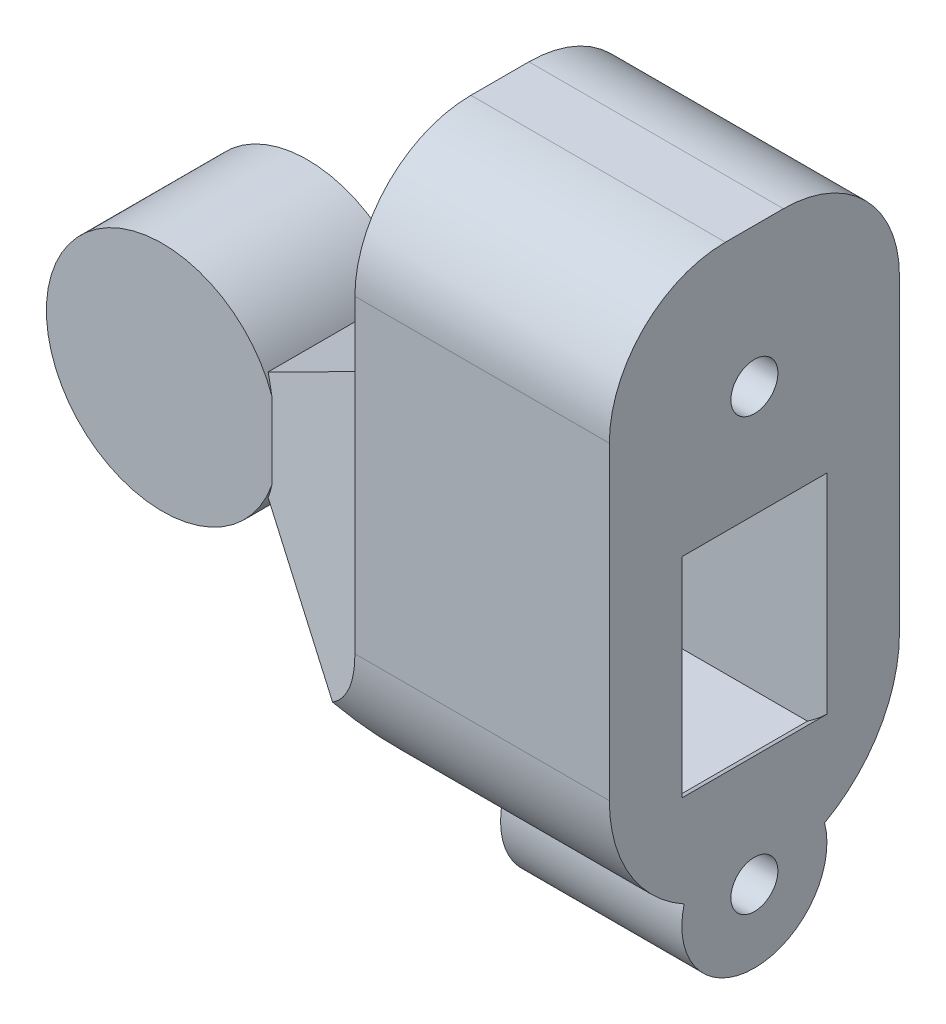
SolidWorks part; units mm, degrees
material "Polycarbonate"
ref_plane "Front Plane" through (0, 0, 0) normal (0, 0, 1) x (1, 0, 0)
ref_plane "Top Plane" through (0, 0, 0) normal (0, 1, 0) x (1, 0, 0)
ref_plane "Right Plane" through (0, 0, 0) normal (1, 0, 0) x (0, 0, -1)
sketch "Sketch1" plane through (0, 0, 0) normal (0, 0, 1) x (1, 0, 0)
  line L3 (4.4873, -2.3813) -> (4.4873, 2.3813)
  arc A0 (4.4873, 2.3813) -> (4.4873, -2.3813) centre (0, 0) ccw
  dimension "D1" = 10.16
  dimension "D2" = 4.7625
extrude "Boss-Extrude1" add sketch "Sketch1" along normal blind 6.35
sketch "Sketch2" plane through (0, 0, 6.35) normal (0, 0, 1) x (1, 0, 0)
  line L1 (21.806, 6.3475) -> (22.74, 7.6311) construction
  line L3 (21.806, -6.3475) -> (22.74, -7.6311) construction
  line L4 (21.806, 6.3475) -> (21.806, -6.3475) construction
  line L5 (4.4873, -2.3813) -> (11.6004, -7.6061)
  line L6 (4.4873, 2.3813) -> (11.6004, 7.6061)
  line L7 (4.4873, 2.3813) -> (4.4873, -2.3813)
  line L9 (22.74, 7.6311) -> (22.74, -7.6311)
  line L10 (14.0937, -9.4375) -> (22.74, -9.4375)
  line L11 (22.74, -9.4375) -> (22.74, -7.6311)
  line L12 (11.6004, -7.6061) -> (14.0937, -9.4375)
  line L13 (11.6004, 7.6061) -> (11.6004, 15.5436)
  line L14 (11.6004, 15.5436) -> (22.74, 15.5436)
  line L16 (4.4873, -2.3813) -> (4.4873, 2.3813) construction
  line L19 (22.74, 7.6311) -> (22.74, 15.5436)
  arc A0 (21.806, 6.3475) -> (21.806, -6.3475) centre (17.1873, 0) ccw construction
  arc A1 (22.74, 7.6311) -> (11.6004, 7.6061) centre (17.1873, 0) ccw construction
  arc A2 (11.6004, -7.6061) -> (22.74, -7.6311) centre (17.1873, 0) ccw construction
  point P9 (21.806, 0)
  point P12 (4.4873, 0)
  line M22 (4.4873, -2.3813) -> (4.4873, 2.3813)
  dimension "D1" = 15.7
  dimension "D2" = 18.875
  dimension "D3" = 12.6949
  dimension "D4" = 12.7
  dimension "D5" = 7.9375
extrude "Boss-Extrude2" add sketch "Sketch2" against normal offset from surface (12.7 mm away) 3.175 from offset 3.175 contours L5 L12 L10 L11 L9 L6 M22 | L10 L11 L9 L19 L14 L13 L6 L7 L5 L12 region at (15.4601, 2.5062, 6.35) up to face at (-0.2963, 0, 0) offset beyond the face yes
sketch "Sketch10" plane through (0, 0, -3.175) normal (0, 0, -1) x (-1, 0, 0)
  line L1 (-22.74, -4.572) -> (-22.74, 4.572)
  line L2 (-22.74, -9.4375) -> (-22.74, 15.5436) construction
  line L3 (-21.8893, -5.2609) -> (-14.7773, -5.2609)
  line L4 (-14.7773, 5.2609) -> (-21.8893, 5.2609)
  line L5 (-12.834, -3.175) -> (-12.834, 3.175)
  arc A0 (-22.74, -4.572) -> (-21.8893, -5.2609) centre (-18.3333, 0) ccw
  arc A1 (-14.7773, -5.2609) -> (-12.834, -3.175) centre (-18.3333, 0) ccw
  arc A2 (-21.8893, 5.2609) -> (-22.74, 4.572) centre (-18.3333, 0) ccw
  arc A3 (-12.834, 3.175) -> (-14.7773, 5.2609) centre (-18.3333, 0) ccw
  circle A4 centre (-18.3333, 0) radius 5.08 construction
  point P3 (-22.74, 0)
  dimension "D1" = 12.7
  dimension "D5" = 10.16
  dimension "D2" = 9.144
  dimension "D3" = 7.112
  dimension "D4" = 6.35
extrude "Cut-Extrude1" cut sketch "Sketch10" against normal blind 6.35 from offset 3.175 offset against normal yes
hole_wizard "#1 Clearance Hole1" positions "Sketch7" profile "Sketch8" hole size "#1" standard "ANSI Inch" end condition through all
sketch "Sketch7" plane through (22.74, 0, 0) normal (1, 0, 0) x (0, 0, -1)
  line L0 (3.175, -9.4375) -> (-9.525, -9.4375) construction
  point P0 (-3.175, 9.4375)
  dimension "D1" = 18.875
sketch "Sketch8" plane through (22.74, 9.4375, 3.175) normal (0, 1, 0) x (0, 0, -1)
  line L0 (0, 0) -> (0, 27.82)
  line L1 (0, 27.82) -> (1.0287, 27.82)
  line L2 (1.0287, 27.82) -> (1.0287, 0)
  line L5 (1.0287, 0) -> (0, 0)
  line L11 (0, -6.35) -> (0, 107.95) construction
  dimension "Thru Hole Dia." = 2.0574
  dimension "Thru Hole Depth" = 27.82
fillet "Fillet4" 2 edges at (18.4169, -9.4375, -3.175) (18.4169, -9.4375, 9.525) type full round first side face at (13.107, 2.8312, -3.175) second side face at (13.107, 2.8312, 9.525) middle face at (18.4169, -9.4375, 3.175)
fillet "Fillet5" radius 5.08 2 edges at (17.1702, 15.5436, 9.525) (17.1702, 15.5436, -3.175)
chamfer "Chamfer3" distance 7.112 angle 25 2 edges at (4.4873, 0, -3.175) (4.4873, 0, 9.525) first distance on face at (11.872, 3.194, -3.175) first distance on face at (11.872, 3.194, 9.525)
sketch "Sketch9" plane through (22.74, 0, 0) normal (1, 0, 0) x (0, 0, -1)
  line L0 (2.414, 13.138) -> (5.4394, 15.2565)
  line L1 (7.2606, 12.6557) -> (3.175, 9.7949)
  line L2 (3.175, -3.0875) -> (3.175, 10.4636) construction
  line L3 (3.175, 9.7949) -> (3.175, 10.4636)
  line L4 (-3.175, 15.5436) -> (9.5717, 15.5436) construction
  line L5 (-1.905, 15.5436) -> (-4.445, 15.5436) construction
  line L6 (-3.175, 15.5436) -> (-3.175, 9.4375) construction
  line L7 (-9.525, 9.7949) -> (-9.525, 10.4636)
  line L8 (-13.6106, 12.6557) -> (-9.525, 9.7949)
  line L9 (-8.764, 13.138) -> (-11.7894, 15.2565)
  arc A0 (3.175, 10.4636) -> (-1.905, 15.5436) centre (-1.905, 10.4636) ccw construction
  arc A1 (5.4394, 15.2565) -> (7.2606, 12.6557) centre (6.35, 13.9561) cw
  arc A2 (3.175, 10.4636) -> (2.414, 13.138) centre (-1.905, 10.4636) ccw
  arc A3 (-9.525, 10.4636) -> (-8.764, 13.138) centre (-4.445, 10.4636) cw
  arc A4 (-11.7894, 15.2565) -> (-13.6106, 12.6557) centre (-12.7, 13.9561) ccw
  dimension "D1" = 1.5875
  dimension "D2" = 125
  dimension "D3" = 9.525
sketch "Sketch11" plane through (22.74, 0, 0) normal (1, 0, 0) x (0, 0, -1)
  arc A0 (-6.2492, -8.6438) -> (-0.1008, -8.6438) centre (-3.175, -9.4375) ccw
  arc A1 (-9.525, -3.0875) -> (3.175, -3.0875) centre (-3.175, -3.0875) ccw construction
  arc A2 (-6.2492, -8.6438) -> (-0.1008, -8.6438) centre (-3.175, -3.0875) ccw
  dimension "D1" = 6.35
extrude "Boss-Extrude3" add sketch "Sketch11" against normal blind 7.9375
hole_wizard "#1 Clearance Hole2" positions "Sketch12" profile "Sketch13" hole size "#1" standard "ANSI Inch" end condition through all
sketch "Sketch12" plane through (22.74, 0, 0) normal (1, 0, 0) x (0, 0, -1)
  point P0 (-3.175, -9.4375)
sketch "Sketch13" plane through (22.74, -9.4375, 3.175) normal (0, 1, 0) x (0, 0, -1)
  line L0 (0, 0) -> (0, 27.82)
  line L1 (0, 27.82) -> (1.0287, 27.82)
  line L2 (1.0287, 27.82) -> (1.0287, 0)
  line L5 (1.0287, 0) -> (0, 0)
  line L11 (0, -6.35) -> (0, 107.95) construction
  dimension "Thru Hole Dia." = 2.0574
  dimension "Thru Hole Depth" = 27.82
sketch "Sketch14" plane through (14.8025, 0, 0) normal (-1, 0, 0) x (0, 0, 1)
  circle A0 centre (3.175, -9.4375) radius 3.175
extrude "Cut-Extrude2" cut sketch "Sketch14" along normal through all
